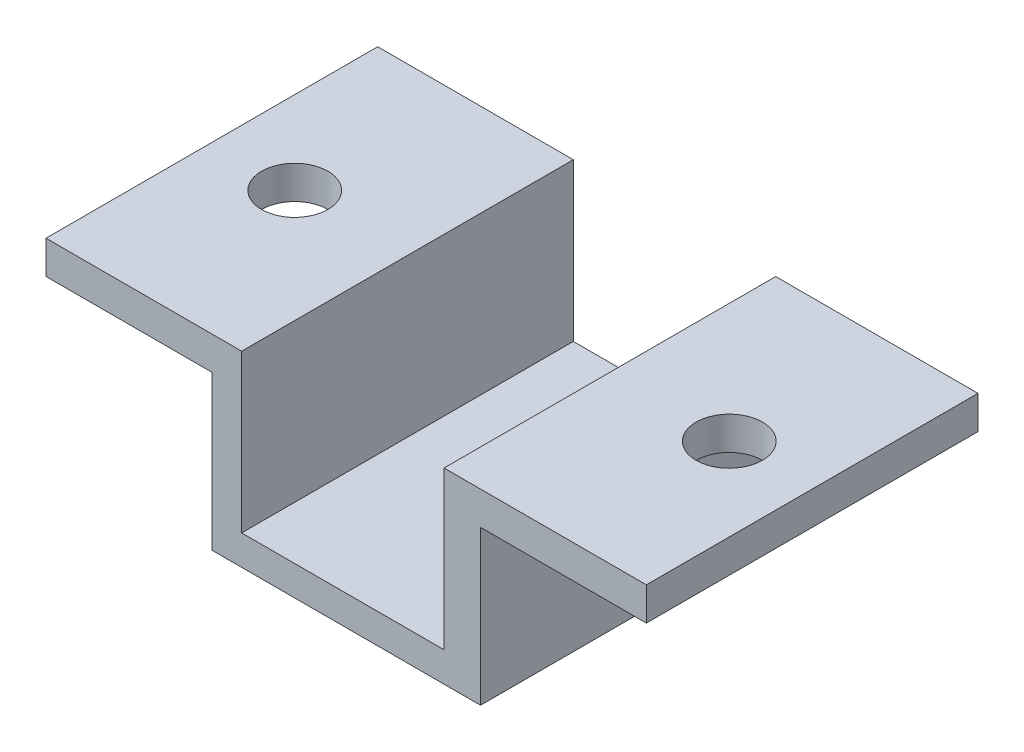
SolidWorks part; units mm, degrees
ref_plane "Front Plane" through (0, 0, 0) normal (0, 0, 1) x (1, 0, 0)
ref_plane "Top Plane" through (0, 0, 0) normal (0, 1, 0) x (1, 0, 0)
ref_plane "Right Plane" through (0, 0, 0) normal (1, 0, 0) x (0, 0, -1)
sketch "Sketch2" plane through (0, 0, 0) normal (0, 1, 0) x (1, 0, 0)
  line L1 (0, 0) -> (45.98, 0)
  line L2 (0, 0) -> (0, 25.4)
  line L3 (0, 25.4) -> (45.98, 25.4)
  line L4 (45.98, 0) -> (45.98, 25.4)
  dimension "D1" = 25.4
  dimension "D2" = 45.98
extrude "Boss-Extrude1" add sketch "Sketch2" along normal blind 14.34
sketch "Sketch3" plane through (0, 14.34, 0) normal (0, 1, 0) x (1, 0, 0)
  line L0 (0, 0) -> (45.98, 0) construction
  line L1 (14.986, 0) -> (30.486, 0)
  line L2 (14.986, 0) -> (14.986, 25.4)
  line L3 (14.986, 25.4) -> (30.486, 25.4)
  line L4 (30.486, 0) -> (30.486, 25.4)
  line L5 (45.98, 25.4) -> (0, 25.4) construction
  line L6 (0, 25.4) -> (0, 0) construction
  dimension "D1" = 15.5
  dimension "D2" = 14.986
extrude "Cut-Extrude1" cut sketch "Sketch3" against normal blind 12.054
sketch "Sketch4" plane through (0, 0, 0) normal (0, -1, 0) x (-1, 0, 0)
  line L0 (-45.98, 25.4) -> (0, 25.4) construction
  line L1 (0, 0) -> (-12.7, 0)
  line L2 (0, 0) -> (0, 25.4)
  line L3 (0, 25.4) -> (-12.7, 25.4)
  line L4 (-12.7, 0) -> (-12.7, 25.4)
  dimension "D1" = 12.7
extrude "Cut-Extrude2" cut sketch "Sketch4" against normal blind 11.8
sketch "Sketch5" plane through (0, 0, 0) normal (0, -1, 0) x (-1, 0, 0)
  line L0 (-45.98, 25.4) -> (-12.7, 25.4) construction
  line L1 (-45.98, 0) -> (-33.28, 0)
  line L2 (-45.98, 0) -> (-45.98, 25.4)
  line L3 (-45.98, 25.4) -> (-33.28, 25.4)
  line L4 (-33.28, 0) -> (-33.28, 25.4)
  dimension "D1" = 12.7
extrude "Cut-Extrude3" cut sketch "Sketch5" against normal blind 11.8
sketch "Sketch6" plane through (0, 11.8, 0) normal (0, -1, 0) x (-1, 0, 0)
  line L0 (-12.7, 0) -> (0, 0) construction
  line L1 (0, 0) -> (0, 25.4) construction
  circle A0 centre (-6.35, 12.7) radius 2.54
  point P6 (0, 12.7)
  dimension "D1" = 12.7
  dimension "D2" = 6.35
extrude "Cut-Extrude4" cut sketch "Sketch6" against normal blind 2.54
sketch "Sketch7" plane through (0, 11.8, 0) normal (0, -1, 0) x (-1, 0, 0)
  line L0 (-45.98, 0) -> (-33.28, 0) construction
  line L1 (-45.98, 25.4) -> (-45.98, 0) construction
  circle A0 centre (-39.63, 12.7) radius 2.54
  dimension "D1" = 12.7
  dimension "D2" = 6.35
extrude "Cut-Extrude5" cut sketch "Sketch7" against normal blind 2.54
